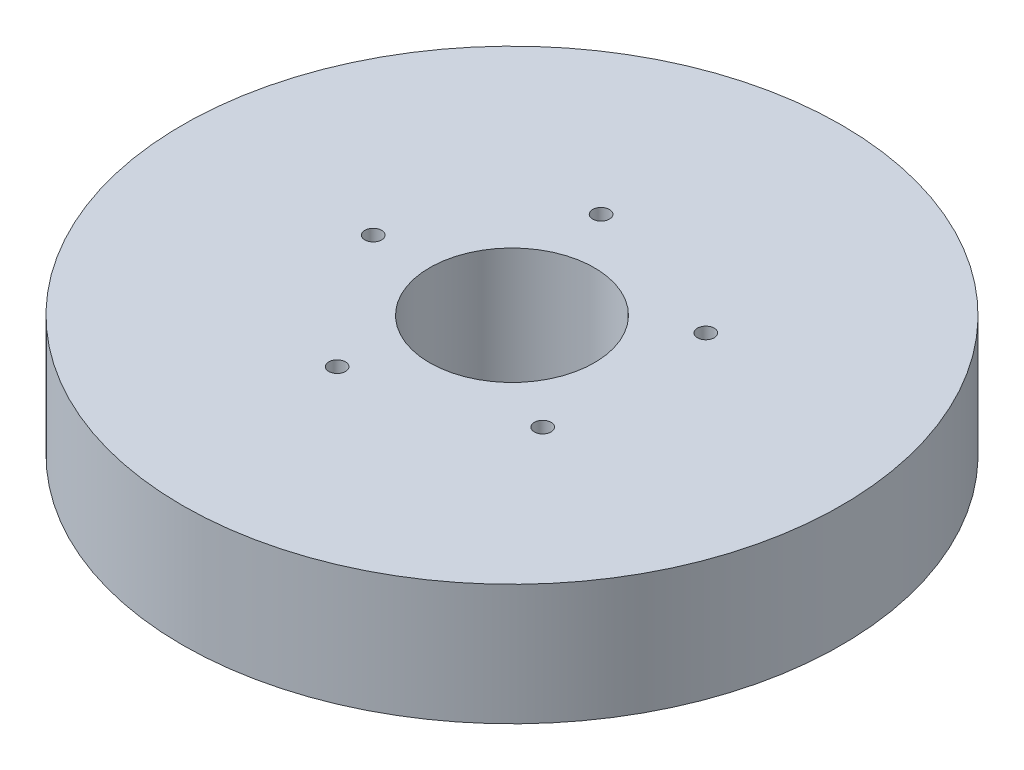
SolidWorks part; units mm, degrees
ref_plane "Front Plane" through (0, 0, 0) normal (0, 0, 1) x (1, 0, 0)
ref_plane "Top Plane" through (0, 0, 0) normal (0, 1, 0) x (1, 0, 0)
ref_plane "Right Plane" through (0, 0, 0) normal (1, 0, 0) x (0, 0, -1)
sketch "Sketch1" plane through (0, 0, 0) normal (0, 1, 0) x (1, 0, 0)
  circle A0 centre (0, 0) radius 60
  dimension "FLANGE_OD" = 120
extrude "Boss-Extrude1" add sketch "Sketch1" along normal blind 22
sketch "Sketch2" plane through (0, 0, 0) normal (0, 1, 0) x (1, 0, 0)
  circle A0 centre (0, 0) radius 15
  dimension "BORE_D" = 30
extrude "Cut-Extrude1" cut sketch "Sketch2" along normal through all
sketch "Sketch3" plane through (0, 22, 0) normal (0, 1, 0) x (1, 0, 0)
  circle A0 centre (0, 0) radius 25.2627 construction
  circle A1 centre (-25.2627, 0) radius 1.5262
  dimension "BOLT_D" = 3.0524
  dimension "BOLT_PCD" = 50.5255
extrude "Cut-Extrude2" cut sketch "Sketch3" against normal blind 13.9336
pattern_circular "CirPattern1" count 5 over 360 about axis through (0, 0, 0) along (0, 1, 0) of "Cut-Extrude2"
